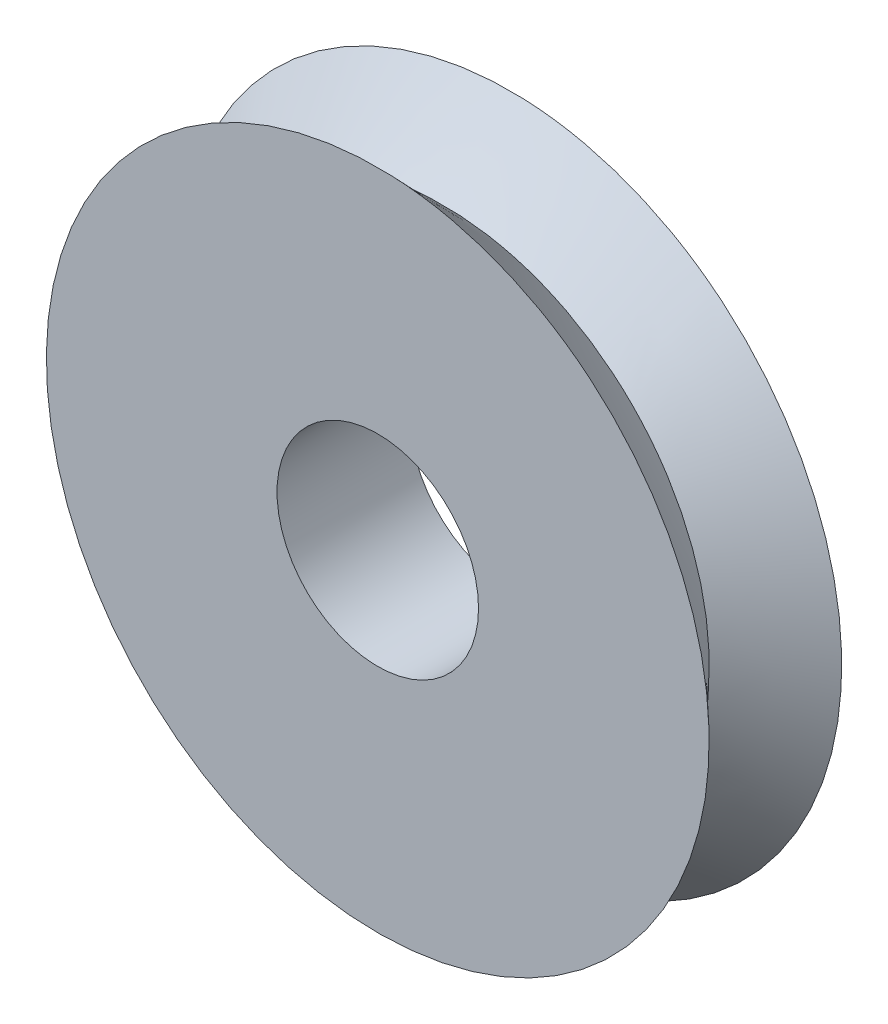
SolidWorks part; units mm, degrees
ref_plane "Front Plane" through (0, 0, 0) normal (0, 0, 1) x (1, 0, 0)
ref_plane "Top Plane" through (0, 0, 0) normal (0, 1, 0) x (1, 0, 0)
ref_plane "Right Plane" through (0, 0, 0) normal (1, 0, 0) x (0, 0, -1)
sketch "Sketch1" plane through (0, 0, 0) normal (0, 0, 1) x (1, 0, 0)
  circle A0 centre (0, 0) radius 4
ref_plane "Plane1" through (0, 0, 1) normal (0, 0, 1) x (1, 0, 0)
sketch "Sketch2" plane through (0, 0, 1) normal (0, 0, 1) x (1, 0, 0)
  circle A0 centre (0, 0) radius 5
loft "Loft1" add profiles "Sketch1", "Sketch2" connector at (-2.2066, -3.3363, 0) connector at (-1.7967, -4.666, 1)
mirror "Mirror1" about plane through (0, 0, 0) normal (0, 0, 1) of bodies 101
sketch "Sketch3" plane through (0, 0, 1) normal (0, 0, 1) x (1, 0, 0)
  line L0 (0, -1.52) -> (0, 0.58)
  line L1 (-1.405, 0.58) -> (1.405, 0.58)
  circle A0 centre (0, 0) radius 1.52
  point P8 (0, 0.58)
extrude "Cut-Extrude1" cut sketch "Sketch3" against normal up to next contours L1 A0 L0 | L0 A0 L1 | L1 A0 region at (-0.6761, -0.3457, 1) region at (0.6761, -0.3457, 1) region at (0, 0.9682, 1)
